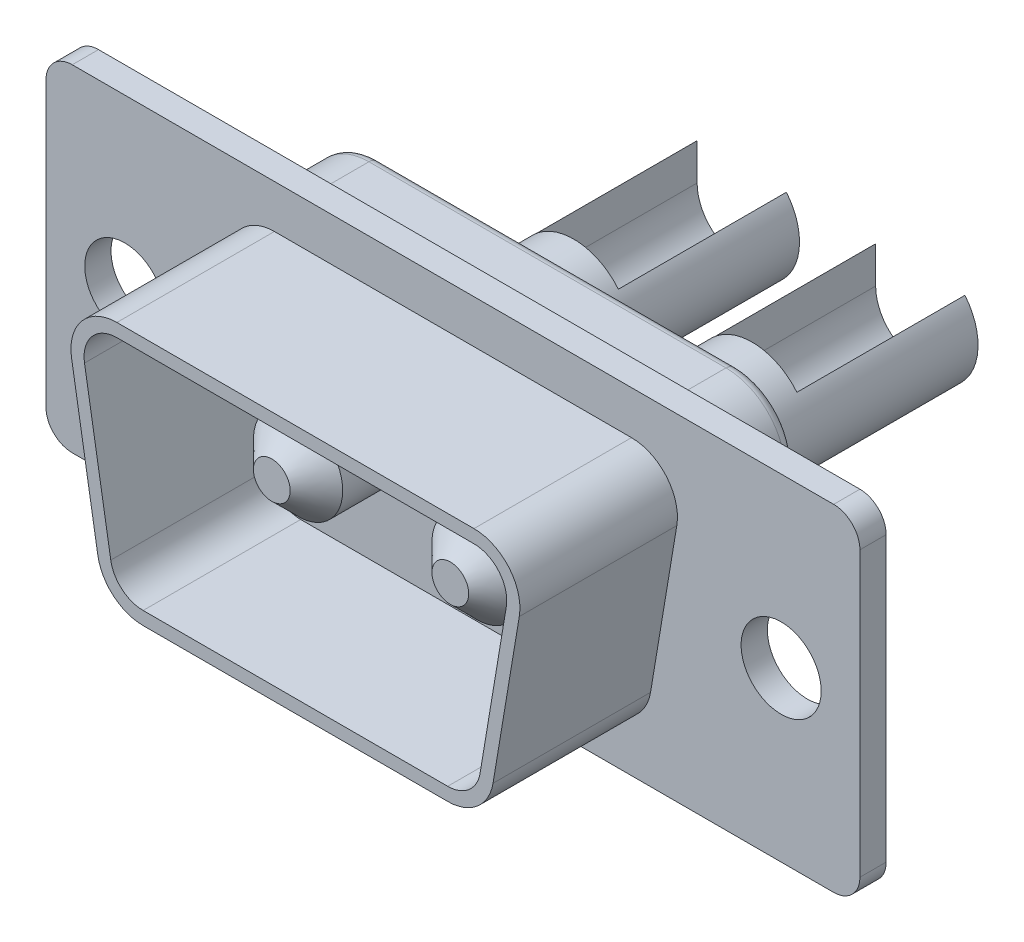
SolidWorks part; units mm, degrees
ref_plane "Top Plane" through (0, 0, 0) normal (0, 0, 1) x (1, 0, 0)
ref_plane "Right Plane" through (0, 0, 0) normal (0, 1, 0) x (1, 0, 0)
ref_plane "Front Plane" through (0, 0, 0) normal (1, 0, 0) x (0, 0, -1)
sketch "Sketch1" plane through (0, 0, 0) normal (0, 0, 1) x (1, 0, 0)
  line L0 (-15.5, 6.4) -> (15.5, -6.4) construction
  line L1 (-15.5, 6.4) -> (15.5, 6.4)
  line L2 (-15.5, 6.4) -> (-15.5, -6.4)
  line L3 (-15.5, -6.4) -> (15.5, -6.4)
  line L4 (15.5, 6.4) -> (15.5, -6.4)
  line L5 (0, 6.4) -> (0, -6.4) construction
  circle A0 centre (-12.5, 0) radius 1.525 construction
  circle A1 centre (12.5, 0) radius 1.525 construction
  dimension "D3" = 25
  dimension "D4" = 3.05
  dimension "D1" = 31
  dimension "D2" = 12.8
extrude "Boss-Extrude1" add sketch "Sketch1" along normal mid plane 1
sketch "Sketch2" plane through (0, 0, 0.5) normal (0, 0, 1) x (1, 0, 0)
  circle A0 centre (12.5, 0) radius 1.525 construction
  circle A1 centre (-12.5, 0) radius 1.525 construction
  circle A2 centre (12.5, 0) radius 1.525
  circle A3 centre (-12.5, 0) radius 1.525
extrude "Cut-Extrude1" cut sketch "Sketch2" against normal through all
sketch "Sketch3" plane through (0, 0, 0.5) normal (0, 0, 1) x (1, 0, 0)
  line L0 (0, -4.25) -> (0, 4.25) construction
  line L1 (-7.033, -3.2055) -> (-8.033, 2.7945)
  line L2 (-5.8, -4.25) -> (5.8, -4.25)
  line L3 (7.033, -3.2055) -> (8.033, 2.7945)
  line L4 (-6.8, 4.25) -> (6.8, 4.25)
  line L5 (-7.5262, -3.2877) -> (-8.5262, 2.7123) construction
  line L6 (-6.8, 4.75) -> (6.8, 4.75) construction
  line L7 (7.5262, -3.2877) -> (8.5262, 2.7123) construction
  line L8 (-5.8, -4.75) -> (5.8, -4.75) construction
  arc A0 (-6.8, 4.25) -> (-8.033, 2.7945) centre (-6.8, 3) ccw
  arc A1 (-7.033, -3.2055) -> (-5.8, -4.25) centre (-5.8, -3) ccw
  arc A2 (7.033, -3.2055) -> (5.8, -4.25) centre (5.8, -3) cw
  arc A3 (6.8, 4.25) -> (8.033, 2.7945) centre (6.8, 3) cw
  arc A4 (-6.8, 4.75) -> (-8.5262, 2.7123) centre (-6.8, 3) ccw construction
  arc A5 (6.8, 4.75) -> (8.5262, 2.7123) centre (6.8, 3) cw construction
  arc A6 (7.5262, -3.2877) -> (5.8, -4.75) centre (5.8, -3) cw construction
  arc A7 (-7.5262, -3.2877) -> (-5.8, -4.75) centre (-5.8, -3) ccw construction
  point P13 (-8.05, 3)
  point P18 (8.05, 3)
  dimension "D1" = 2.5
  dimension "D2" = 16.1
  dimension "D3" = 1
  dimension "D4" = 8.5
  dimension "D5" = 0.5
extrude "Boss-Extrude2" [suppressed] add sketch "Sketch3" along normal blind 6
sketch "Sketch10" plane through (0, 0, 0.5) normal (0, 0, 1) x (1, 0, 0)
  line L0 (-7.033, -3.2055) -> (-8.033, 2.7945) construction
  line L1 (-5.8, -4.25) -> (5.8, -4.25) construction
  line L2 (7.033, -3.2055) -> (8.033, 2.7945) construction
  line L3 (-6.8, 4.25) -> (6.8, 4.25) construction
  line L4 (-7.033, -3.2055) -> (-8.033, 2.7945)
  line L5 (-5.8, -4.25) -> (5.8, -4.25)
  line L6 (7.033, -3.2055) -> (8.033, 2.7945)
  line L7 (-6.8, 4.25) -> (6.8, 4.25)
  line L8 (-7.5262, -3.2877) -> (-8.5262, 2.7123) construction
  line L9 (-5.8, -4.75) -> (5.8, -4.75) construction
  line L10 (7.5262, -3.2877) -> (8.5262, 2.7123) construction
  line L11 (-6.8, 4.75) -> (6.8, 4.75) construction
  line L12 (-7.5262, -3.2877) -> (-8.5262, 2.7123)
  line L13 (-5.8, -4.75) -> (5.8, -4.75)
  line L14 (7.5262, -3.2877) -> (8.5262, 2.7123)
  line L15 (-6.8, 4.75) -> (6.8, 4.75)
  arc A0 (-6.8, 4.25) -> (-8.033, 2.7945) centre (-6.8, 3) ccw construction
  arc A1 (-7.033, -3.2055) -> (-5.8, -4.25) centre (-5.8, -3) ccw construction
  arc A2 (5.8, -4.25) -> (7.033, -3.2055) centre (5.8, -3) ccw construction
  arc A3 (8.033, 2.7945) -> (6.8, 4.25) centre (6.8, 3) ccw construction
  arc A4 (-6.8, 4.25) -> (-8.033, 2.7945) centre (-6.8, 3) ccw
  arc A5 (-7.033, -3.2055) -> (-5.8, -4.25) centre (-5.8, -3) ccw
  arc A6 (5.8, -4.25) -> (7.033, -3.2055) centre (5.8, -3) ccw
  arc A7 (8.033, 2.7945) -> (6.8, 4.25) centre (6.8, 3) ccw
  arc A8 (-6.8, 4.75) -> (-8.5262, 2.7123) centre (-6.8, 3) ccw construction
  arc A9 (-7.5262, -3.2877) -> (-5.8, -4.75) centre (-5.8, -3) ccw construction
  arc A10 (5.8, -4.75) -> (7.5262, -3.2877) centre (5.8, -3) ccw construction
  arc A11 (8.5262, 2.7123) -> (6.8, 4.75) centre (6.8, 3) ccw construction
  arc A12 (-6.8, 4.75) -> (-8.5262, 2.7123) centre (-6.8, 3) ccw
  arc A13 (-7.5262, -3.2877) -> (-5.8, -4.75) centre (-5.8, -3) ccw
  arc A14 (5.8, -4.75) -> (7.5262, -3.2877) centre (5.8, -3) ccw
  arc A15 (8.5262, 2.7123) -> (6.8, 4.75) centre (6.8, 3) ccw
extrude "Boss-Extrude5" add sketch "Sketch10" along normal blind 6
sketch "Sketch5" plane through (0, 0, -0.5) normal (0, 0, -1) x (-1, 0, 0)
  line L8 (8.0194, -3.3699) -> (9.0194, 2.6301)
  line L9 (-5.8, -5.25) -> (5.8, -5.25)
  line L10 (-9.0194, 2.6301) -> (-8.0194, -3.3699)
  line L11 (6.8, 5.25) -> (-6.8, 5.25)
  line L12 (8.0194, -3.3699) -> (9.0194, 2.6301)
  line L13 (-5.8, -5.25) -> (5.8, -5.25)
  line L14 (-9.0194, 2.6301) -> (-8.0194, -3.3699)
  line L15 (6.8, 5.25) -> (-6.8, 5.25)
  arc A8 (9.0194, 2.6301) -> (6.8, 5.25) centre (6.8, 3) ccw
  arc A9 (5.8, -5.25) -> (8.0194, -3.3699) centre (5.8, -3) ccw
  arc A10 (-8.0194, -3.3699) -> (-5.8, -5.25) centre (-5.8, -3) ccw
  arc A11 (-6.8, 5.25) -> (-9.0194, 2.6301) centre (-6.8, 3) ccw
  arc A12 (9.0194, 2.6301) -> (6.8, 5.25) centre (6.8, 3) ccw
  arc A13 (5.8, -5.25) -> (8.0194, -3.3699) centre (5.8, -3) ccw
  arc A14 (-8.0194, -3.3699) -> (-5.8, -5.25) centre (-5.8, -3) ccw
  arc A15 (-6.8, 5.25) -> (-9.0194, 2.6301) centre (-6.8, 3) ccw
  dimension "D1" = 0.5
extrude "Boss-Extrude3" add sketch "Sketch5" along normal blind 3
sketch "Sketch6" plane through (0, 0, -3.5) normal (0, 0, -1) x (-1, 0, 0)
  line L0 (0, 6.1668) -> (0, -6.0028) construction
  circle A0 centre (-3.4, 0) radius 2.2
  circle A1 centre (3.4, 0) radius 2.2
  dimension "D1" = 6.8
  dimension "D2" = 4.4
extrude "Boss-Extrude4" add sketch "Sketch6" along normal blind 10.4
sketch "Sketch7" plane through (0, 0, -13.9) normal (0, 0, -1) x (-1, 0, 0)
  line L0 (-5.1, 0) -> (-5.1, 1.3964)
  line L1 (-1.7, 0) -> (-1.7, 1.3964)
  line L2 (0, 4.25) -> (0, -4.25) construction
  line L3 (1.7, 0) -> (1.7, 1.3964)
  line L4 (5.1, 0) -> (5.1, 1.3964)
  circle A8 centre (-3.4, 0) radius 1.7
  arc A9 (-5.1, 0) -> (-1.7, 0) centre (-3.4, 0) ccw
  circle A10 centre (-3.4, 0) radius 2.2 construction
  arc A11 (1.7, 1.3964) -> (5.1, 1.3964) centre (3.4, 0) cw
  arc A12 (5.1, 0) -> (1.7, 0) centre (3.4, 0) cw
  arc A13 (-1.7, 1.3964) -> (-5.1, 1.3964) centre (-3.4, 0) ccw
  dimension "D1" = 0.5
extrude "Cut-Extrude2" cut sketch "Sketch7" against normal offset from surface (6.4 mm away) 4 up to face at (-1.2, 0, -3.5)
sketch "Sketch9" [suppressed] plane through (0, 0, 4.5) normal (0, 0, 1) x (1, 0, 0)
  arc A0 (-5.1, 0) -> (-1.7, 0) centre (-3.4, 0) ccw construction
  circle A1 centre (-3.4, 0) radius 1.7
  arc A2 (1.7, 0) -> (5.1, 0) centre (3.4, 0) ccw construction
  circle A3 centre (3.4, 0) radius 1.7
extrude "Cut-Extrude3" [suppressed] cut sketch "Sketch9" against normal blind 4
sketch "Sketch12" plane through (0, 0, 0.5) normal (0, 0, 1) x (1, 0, 0)
  arc A0 (-5.1, 0) -> (-1.7, 0) centre (-3.4, 0) ccw construction
  circle A1 centre (-3.4, 0) radius 1.7
  arc A2 (1.7, 0) -> (5.1, 0) centre (3.4, 0) ccw construction
  circle A3 centre (3.4, 0) radius 1.7
extrude "Boss-Extrude6" add sketch "Sketch12" along normal blind 3.5
chamfer "Chamfer1" distance 1 angle 45 2 edges at (5.1, 0, 4) (-1.7, 0, 4)
fillet "Fillet1" radius 1 4 edges at (15.5, 6.4, 0) (15.5, -6.4, 0) (-15.5, -6.4, 0) (-15.5, 6.4, 0)
fillet "Fillet2" radius 0.4 8 edges at (-8.5168, 4.4543, -3.5) (-8.5194, -0.3699, -3.5) (-7.2543, -4.7168, -3.5) (0, -5.25, -3.5) (7.2543, -4.7168, -3.5) (8.5194, -0.3699, -3.5) (8.5168, 4.4543, -3.5) (0, 5.25, -3.5)
fillet "Fillet4" [suppressed] radius 0.4
